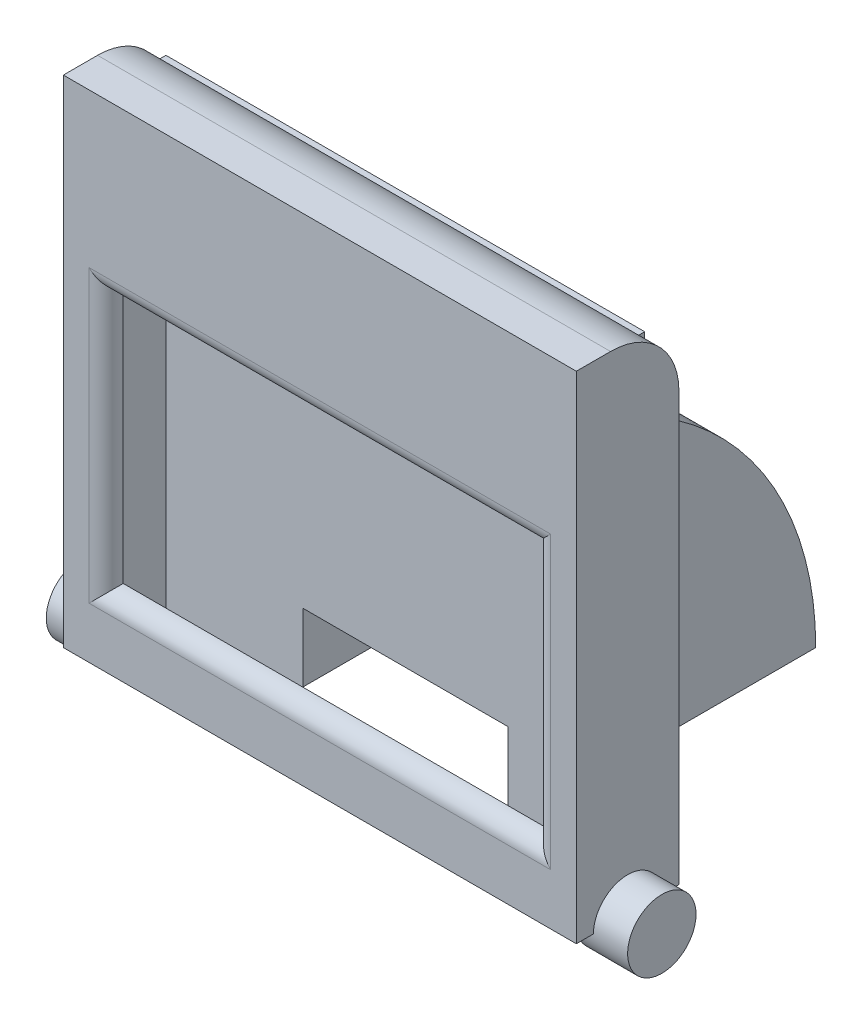
SolidWorks part; units mm, degrees
ref_plane "Plan de face" through (0, 0, 0) normal (0, 0, 1) x (1, 0, 0)
ref_plane "Plan de dessus" through (0, 0, 0) normal (0, 1, 0) x (1, 0, 0)
ref_plane "Plan de droite" through (0, 0, 0) normal (1, 0, 0) x (0, 0, -1)
sketch "Esquisse1" plane through (0, 0, 0) normal (0, 0, 1) x (1, 0, 0)
  line L1 (0, 0) -> (28, 0)
  line L2 (0, 0) -> (0, 28)
  line L3 (0, 28) -> (28, 28)
  line L4 (28, 0) -> (28, 28)
  dimension "D1" = 28
  dimension "D2" = 28
extrude "Boss.-Extru.1" add sketch "Esquisse1" along normal blind 4
shell "Coque1" thickness 1 removed face at (14, 0, 2) outward yes
sketch "Esquisse2" plane through (0, 0, 5) normal (0, 0, 1) x (1, 0, 0)
  line L0 (29, 29) -> (-1, 29) construction
  line L1 (1.5, 19) -> (26.5, 19)
  line L2 (1.5, 19) -> (1.5, 4)
  line L3 (1.5, 4) -> (26.5, 4)
  line L4 (26.5, 19) -> (26.5, 4)
  line L5 (-1, 0) -> (29, 0) construction
  point P4 (14, 19)
  point P7 (14, 29)
  dimension "D1" = 0
  dimension "D2" = 4
  dimension "D3" = 15
  dimension "D4" = 25
extrude "Enlèv. mat.-Extru.1" cut sketch "Esquisse2" against normal up to next
sketch "Esquisse8" plane through (0, 0, -1) normal (0, 0, -1) x (-1, 0, 0)
  line L0 (1, 0) -> (-29, 0) construction
  line L1 (-22, 6) -> (-6, 6)
  line L2 (-22, 6) -> (-22, 0)
  line L3 (-22, 0) -> (-6, 0)
  line L4 (-6, 6) -> (-6, 0)
  point P6 (-14, 6)
  point P7 (-14, 0)
  dimension "D1" = 0
  dimension "D2" = 16
  dimension "D3" = 6
extrude "Boss.-Extru.3" [suppressed] add sketch "Esquisse8" along normal blind 17
sketch "Esquisse10" [suppressed] plane through (0, 0, 0) normal (0, -1, 0) x (1, 0, 0)
  line L0 (22, -19) -> (22, -2) construction
  line L1 (8, -17) -> (20, -17)
  line L2 (8, -17) -> (8, 2.1533)
  line L3 (8, 2.1533) -> (20, 2.1533)
  line L4 (20, -17) -> (20, 2.1533)
  line L5 (6, -19) -> (6, -2) construction
  line L6 (22, -19) -> (6, -19) construction
  dimension "D1" = 2
  dimension "D2" = 2
  dimension "D3" = 2
extrude "Enlèv. mat.-Extru.3" [suppressed] cut sketch "Esquisse10" against normal blind 4
sketch "Esquisse11" [suppressed] plane through (22, 0, 0) normal (1, 0, 0) x (0, 0, -1)
  line L0 (19, 6) -> (19, 0) construction
  circle A0 centre (16, 3) radius 2
  point P4 (19, 3)
  dimension "D1" = 4
  dimension "D2" = 0
  dimension "D3" = 3
extrude "Enlèv. mat.-Extru.4" [suppressed] cut sketch "Esquisse11" against normal blind 2 contours A0
sketch "Esquisse13" [suppressed] plane through (6, 0, 0) normal (-1, 0, 0) x (0, 0, 1)
  line L0 (-19, 0) -> (-19, 6) construction
  circle A0 centre (-16, 3) radius 2
  point P4 (-19, 3)
  dimension "D1" = 4
  dimension "D2" = 3
  dimension "D3" = 0
extrude "Enlèv. mat.-Extru.9" [suppressed] cut sketch "Esquisse13" against normal blind 2
sketch "Esquisse15" [suppressed] plane through (0, 0, 0) normal (0, -1, 0) x (1, 0, 0)
  circle A0 centre (6, -2) radius 2
  dimension "D1" = 4
extrude "Boss.-Extru.5" [suppressed] add sketch "Esquisse15" against normal blind 6
sketch "Esquisse16" [suppressed] plane through (0, 0, 0) normal (0, -1, 0) x (1, 0, 0)
  circle A0 centre (22, -2) radius 2
  dimension "D1" = 4
extrude "Boss.-Extru.6" [suppressed] add sketch "Esquisse16" against normal blind 6
sketch "Esquisse17" [suppressed] plane through (0, 0, 0) normal (0, -1, 0) x (1, 0, 0)
  line L0 (8, -17) -> (20, -17) construction
  line L2 (8, -17) -> (20, -17) construction
  circle A0 centre (14, -19) radius 2
  point P4 (14, -17)
  dimension "D1" = 4
  dimension "D2" = 2
  dimension "D3" = 0
extrude "Boss.-Extru.7" [suppressed] add sketch "Esquisse17" against normal blind 6
sketch "Esquisse18" [suppressed] plane through (0, 0, 0) normal (0, -1, 0) x (1, 0, 0)
  circle A0 centre (6, -2) radius 1
  circle A1 centre (14, -19) radius 1
  circle A2 centre (22, -2) radius 1
  dimension "D1" = 2
  dimension "D2" = 2
  dimension "D3" = 2
extrude "Enlèv. mat.-Extru.10" [suppressed] cut sketch "Esquisse18" against normal blind 5.5
fillet "Congé1" radius 4 1 edges at (14, 29, -1)
fillet "Congé2" [suppressed] radius 2
fillet "Congé3" radius 1 4 edges at (26.5, 11.5, 5) (14, 19, 5) (1.5, 11.5, 5) (14, 4, 5)
sketch "Esquisse19" [suppressed] plane through (0, 0, -19) normal (0, 0, -1) x (-1, 0, 0)
  line L0 (-22, 0) -> (-16, 0) construction
  line L1 (-12, 6) -> (-16, 6) construction
  circle A0 centre (-18, 0) radius 1.25
  point P7 (-14, 6)
  dimension "D1" = 2.5
  dimension "D2" = 0
  dimension "D3" = 4
extrude "Enlèv. mat.-Extru.11" [suppressed] cut sketch "Esquisse19" against normal up to next
sketch "Esquisse20" plane through (0, 0, -1) normal (0, 0, -1) x (-1, 0, 0)
  text T0 "HUMANLAB"
  text T1 "PU1"
extrude "Enlèv. mat.-Extru.12" [suppressed] cut sketch "Esquisse20" against normal blind 1.5
sketch "Esquisse21" plane through (0, 0, -1) normal (0, 0, -1) x (-1, 0, 0)
  line L0 (1, 0) -> (-29, 0) construction
  line L1 (-20, 0) -> (-8, 0)
  line L2 (-20, 0) -> (-20, 4)
  line L3 (-20, 4) -> (-8, 4)
  line L4 (-8, 0) -> (-8, 4)
  point P6 (-14, 0)
  point P9 (-14, 4)
  dimension "D1" = 0
  dimension "D2" = 12
  dimension "D3" = 4
extrude "Enlèv. mat.-Extru.13" cut sketch "Esquisse21" against normal up to next
sketch "Esquisse24" plane through (29, 0, 0) normal (1, 0, 0) x (0, 0, -1)
  line L1 (1, 0) -> (17, 0)
  line L2 (-5, 0) -> (1, 0) construction
  line L3 (1, 0) -> (1, 25) construction
  line L4 (1, 18.7617) -> (1, 0)
  arc A0 (17, 0) -> (1, 18.7617) centre (-2, 0) ccw
extrude "Boss.-Extru.8" add sketch "Esquisse24" along normal mid plane 14 from offset 15 offset against normal yes
shell "Coque2" [suppressed] thickness 1.5
sketch "Esquisse25" plane through (0, 0, -1) normal (0, 0, 1) x (1, 0, 0)
  line L1 (8, 4) -> (20, 4)
  line L2 (8, 4) -> (8, 0)
  line L3 (8, 0) -> (20, 0)
  line L4 (20, 4) -> (20, 0)
sketch "Esquisse26" plane through (0, 0, 0) normal (0, -1, 0) x (1, 0, 0)
  line L0 (7, -1) -> (7, -17) construction
  line L1 (8, -1) -> (20, -1)
  line L2 (8, -1) -> (8, -16)
  line L3 (8, -16) -> (20, -16)
  line L4 (20, -1) -> (20, -16)
  line L5 (21, -1) -> (21, -17) construction
  line L6 (21, -17) -> (7, -17) construction
  dimension "D1" = 1
  dimension "D2" = 1
  dimension "D3" = 1
extrude "Enlèv. mat.-Extru.15" cut sketch "Esquisse26" against normal blind 4
sketch "Esquisse29" plane through (29, 0, 0) normal (1, 0, 0) x (0, 0, -1)
  line L0 (-5, 0) -> (1, 0) construction
  circle A0 centre (-2, 0) radius 2
  dimension "D1" = 4
extrude "Boss.-Extru.9" add sketch "Esquisse29" along normal blind 2 and the other way blind 1
sketch "Esquisse30" plane through (-1, 0, 0) normal (-1, 0, 0) x (0, 0, 1)
  line L0 (5, 0) -> (-1, 0) construction
  circle A0 centre (2, 0) radius 2
  dimension "D1" = 4
extrude "Boss.-Extru.10" add sketch "Esquisse30" along normal blind 2 and the other way blind 1
extrude "Enlèv. mat.-Extru.14" [suppressed] cut sketch "Esquisse25" against normal up to next
